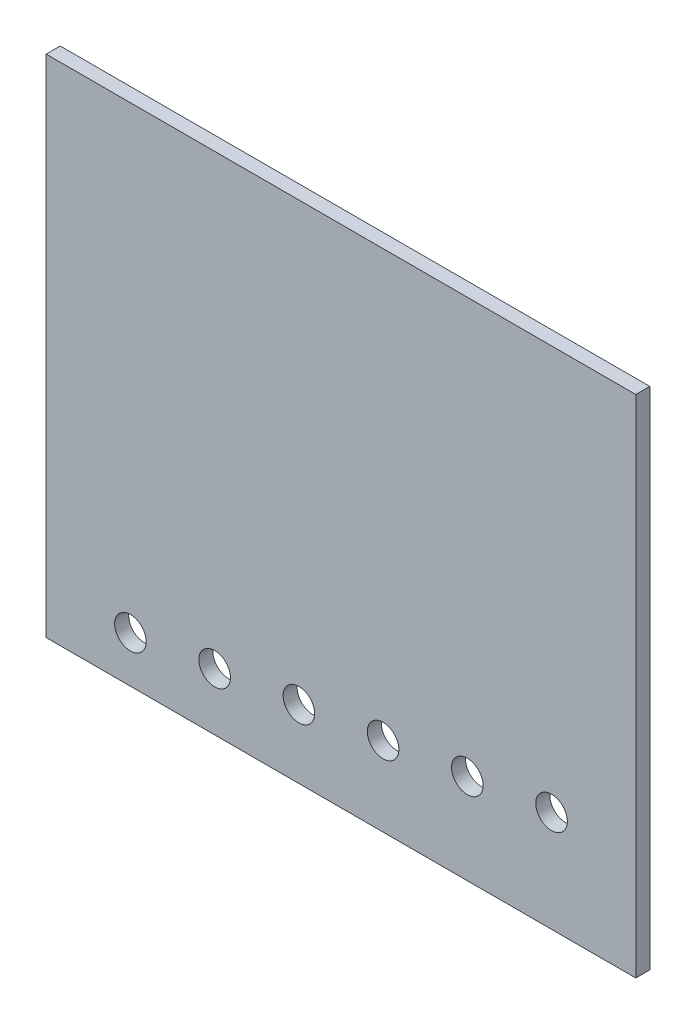
SolidWorks part; units mm, degrees
material "ABS PC"
ref_plane "Front Plane" through (0, 0, 0) normal (0, 0, 1) x (1, 0, 0)
ref_plane "Top Plane" through (0, 0, 0) normal (0, 1, 0) x (1, 0, 0)
ref_plane "Right Plane" through (0, 0, 0) normal (1, 0, 0) x (0, 0, -1)
sketch "Sketch1" plane through (0, 0, 0) normal (0, 0, 1) x (1, 0, 0)
  line L1 (-266.7, 228.6) -> (266.7, 228.6)
  line L2 (-266.7, 228.6) -> (-266.7, -228.6)
  line L3 (-266.7, -228.6) -> (266.7, -228.6)
  line L4 (266.7, 228.6) -> (266.7, -228.6)
  line L5 (-266.7, 228.6) -> (266.7, -228.6) construction
  line L6 (-266.7, -228.6) -> (266.7, 228.6) construction
  point P0 (0, 0)
  dimension "D1" = 457.2
  dimension "D2" = 533.4
extrude "Boss-Extrude4" add sketch "Sketch1" along normal blind 12.7
sketch "Sketch3" plane through (0, 0, 0) normal (0, 0, -1) x (-1, 0, 0)
  line L0 (-266.7, -228.6) -> (-266.7, -127) construction
  line L1 (-266.7, -228.6) -> (-266.7, 228.6) construction
  line L2 (-266.7, -127) -> (266.7, -196.6093) construction
  line L3 (266.7, 228.6) -> (266.7, -228.6) construction
  line L4 (-266.7, -228.6) -> (-190.5, -228.6) construction
  line L5 (-190.5, -228.6) -> (-114.3, -228.6) construction
  line L6 (266.7, -228.6) -> (-266.7, -228.6) construction
  line L7 (-114.3, -228.6) -> (-38.1, -228.6) construction
  line L8 (-38.1, -228.6) -> (38.1, -228.6) construction
  line L9 (38.1, -228.6) -> (114.3, -228.6) construction
  line L10 (114.3, -228.6) -> (190.5, -228.6) construction
  line L11 (190.5, -228.6) -> (266.7, -228.6) construction
  circle A0 centre (-190.5, -136.9442) radius 14.2875
  circle A1 centre (-114.3, -146.8884) radius 14.2875
  circle A2 centre (-38.1, -156.8326) radius 14.2875
  circle A3 centre (38.1, -166.7767) radius 14.2875
  circle A4 centre (114.3, -176.7209) radius 14.2875
  circle A5 centre (190.5, -186.6651) radius 14.2875
  dimension "D8" = 28.575
  dimension "D9" = 28.575
  dimension "D10" = 28.575
  dimension "D11" = 28.575
  dimension "D12" = 28.575
  dimension "D13" = 28.575
  dimension "D1" = 101.6
  dimension "D2" = 76.2
  dimension "D3" = 76.2
  dimension "D4" = 76.2
  dimension "D5" = 76.2
  dimension "D6" = 76.2
  dimension "D7" = 76.2
extrude "Cut-Extrude2" cut sketch "Sketch3" against normal blind 12.7
